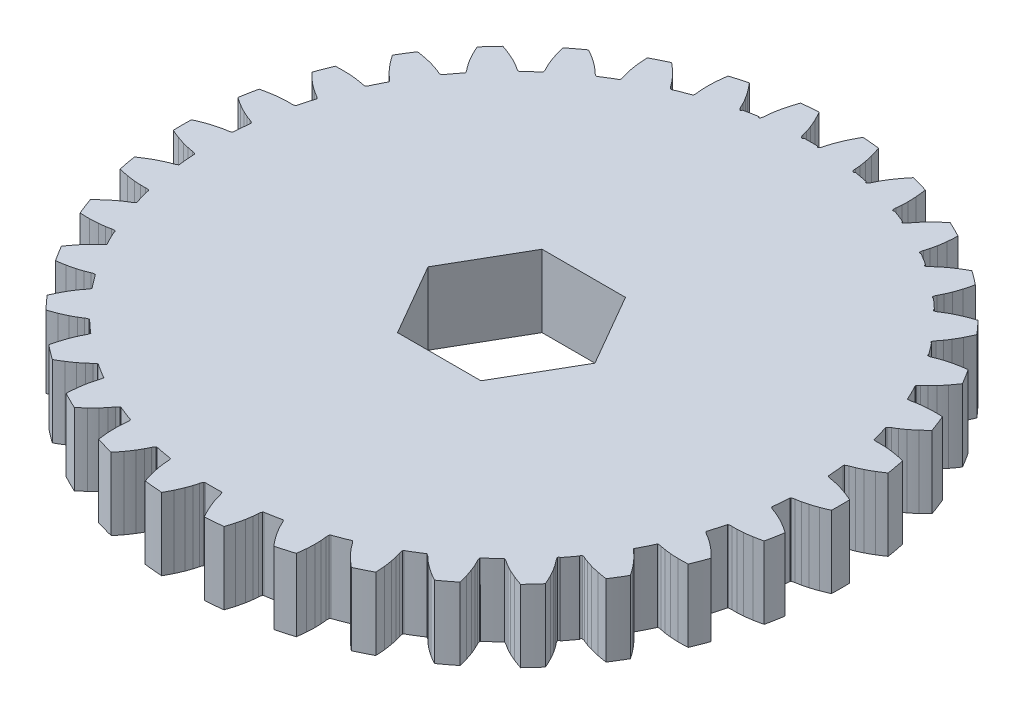
SolidWorks part; units mm, degrees
ref_plane "Front Plane" through (0, 0, 0) normal (0, 0, 1) x (1, 0, 0)
ref_plane "Top Plane" through (0, 0, 0) normal (0, 1, 0) x (1, 0, 0)
ref_plane "Right Plane" through (0, 0, 0) normal (1, 0, 0) x (0, 0, -1)
sketch "Model" plane through (0, 0, 0) normal (0, 1, 0) x (1, 0, 0)
  line L1 (7.3323, 0) -> (3.6662, 6.35)
  line L2 (3.6662, 6.35) -> (-3.6662, 6.35)
  line L3 (-3.6662, 6.35) -> (-7.3323, 0)
  line L4 (-7.3323, 0) -> (-3.6662, -6.35)
  line L5 (-3.6662, -6.35) -> (3.6662, -6.35)
  line L6 (3.6662, -6.35) -> (7.3323, 0)
  circle A0 centre (0, 0) radius 27.7 construction
  arc A1 (26.1185, -2.4202) -> (26.1766, -1.6798) centre (0, 0) ccw
  arc A2 (26.2183, -1.6388) -> (26.1766, -1.6798) centre (26.263, -1.726) ccw
  arc A3 (26.4889, -1.5535) -> (26.2183, -1.6388) centre (26.6041, -2.3907) ccw
  arc A4 (26.4889, -1.5535) -> (26.9416, -1.473) centre (25.6873, 4.2688) ccw
  arc A5 (26.9416, -1.473) -> (27.4742, -1.3382) centre (25.1508, 6.7249) ccw
  arc A6 (27.4742, -1.3382) -> (28.1662, -1.11) centre (24.8202, 7.8723) ccw
  arc A7 (28.1662, -1.11) -> (28.9229, -0.7986) centre (23.9466, 10.2174) ccw
  arc A8 (28.9229, -0.7986) -> (28.9229, 0.7986) centre (0, 0) ccw
  arc A9 (28.9229, 0.7986) -> (28.1662, 1.11) centre (23.9466, -10.2174) ccw
  arc A10 (28.1662, 1.11) -> (27.4742, 1.3382) centre (24.8202, -7.8723) ccw
  arc A11 (27.4742, 1.3382) -> (26.9416, 1.473) centre (25.1508, -6.7249) ccw
  arc A12 (26.9416, 1.473) -> (26.4889, 1.5535) centre (25.6873, -4.2688) ccw
  arc A13 (26.2183, 1.6388) -> (26.4889, 1.5535) centre (26.6041, 2.3907) ccw
  arc A14 (26.1675, 1.6852) -> (26.2183, 1.6388) centre (26.2566, 1.7318) ccw
  arc A15 (26.1675, 1.6852) -> (26.0357, 3.1176) centre (0, 0) ccw
  arc A16 (26.073, 3.2067) -> (26.0357, 3.1176) centre (26.133, 3.1292) ccw
  arc A17 (26.3233, 3.3403) -> (26.073, 3.2067) centre (26.5904, 2.5385) ccw
  arc A18 (26.3233, 3.3403) -> (26.7535, 3.5026) centre (24.4655, 8.9161) ccw
  arc A19 (26.7535, 3.5026) -> (27.2523, 3.7329) centre (23.4869, 11.2318) ccw
  arc A20 (27.2523, 3.7329) -> (27.8906, 4.0844) centre (22.951, 12.2989) ccw
  arc A21 (27.8906, 4.0844) -> (28.5771, 4.5296) centre (21.6614, 14.4436) ccw
  arc A22 (28.5771, 4.5296) -> (28.2837, 6.0995) centre (0, 0) ccw
  arc A23 (28.2837, 6.0995) -> (27.4827, 6.2666) centre (25.4163, -5.6432) ccw
  arc A24 (27.4827, 6.2666) -> (26.7605, 6.3638) centre (25.8441, -3.1775) ccw
  arc A25 (26.7605, 6.3638) -> (26.2122, 6.3984) centre (25.9582, -1.9889) ccw
  arc A26 (26.2122, 6.3984) -> (25.7524, 6.3943) centre (26.0343, 0.5239) ccw
  arc A27 (25.4707, 6.4285) -> (25.7524, 6.3943) centre (25.7119, 7.2385) ccw
  arc A28 (25.4168, 6.447) -> (25.4707, 6.4285) centre (25.4771, 6.5347) ccw
  arc A29 (25.4168, 6.447) -> (25.0195, 7.8485) centre (0, 0) ccw
  arc A30 (25.0398, 7.943) -> (25.0195, 7.8485) centre (25.113, 7.8779) ccw
  arc A31 (25.2613, 8.1203) -> (25.0398, 7.943) centre (25.6712, 7.3813) ccw
  arc A32 (25.2613, 8.1203) -> (25.6544, 8.3589) centre (22.4106, 13.2599) ccw
  arc A33 (25.6544, 8.3589) -> (26.1024, 8.677) centre (21.0231, 15.3563) ccw
  arc A34 (26.1024, 8.677) -> (26.6652, 9.1398) centre (20.3003, 16.3068) ccw
  arc A35 (26.6652, 9.1398) -> (27.2583, 9.7035) centre (18.6386, 18.1779) ccw
  arc A36 (27.2583, 9.7035) -> (26.6813, 11.1928) centre (0, 0) ccw
  arc A37 (26.6813, 11.1928) -> (25.8632, 11.2099) centre (26.0205, -0.8769) ccw
  arc A38 (25.8632, 11.2099) -> (25.1355, 11.1727) centre (25.9879, 1.6254) ccw
  arc A39 (25.1355, 11.1727) -> (24.5902, 11.1059) centre (25.8817, 2.8148) ccw
  arc A40 (24.5902, 11.1059) -> (24.139, 11.0175) centre (25.4948, 5.2988) ccw
  arc A41 (23.8558, 10.9993) -> (24.139, 11.0175) centre (23.944, 11.8398) ccw
  arc A42 (23.8034, 10.9988) -> (23.8558, 10.9993) centre (23.8287, 11.1089) ccw
  arc A43 (23.8034, 10.9988) -> (23.1514, 12.3122) centre (0, 0) ccw
  arc A44 (23.154, 12.4088) -> (23.1514, 12.3122) centre (23.2379, 12.3582) ccw
  arc A45 (23.3391, 12.6238) -> (23.154, 12.4088) centre (23.8778, 11.9727) ccw
  arc A46 (23.3391, 12.6238) -> (23.6816, 12.9306) centre (19.5926, 17.152) ccw
  arc A47 (23.6816, 12.9306) -> (24.0635, 13.3255) centre (17.8434, 18.9578) ccw
  arc A48 (24.0635, 13.3255) -> (24.5317, 13.8838) centre (16.9583, 19.7593) ccw
  arc A49 (24.5317, 13.8838) -> (25.0418, 14.5927) centre (14.981, 21.2932) ccw
  arc A50 (25.0418, 14.5927) -> (24.225, 15.9119) centre (0, 0) ccw
  arc A51 (24.225, 15.9119) -> (23.363, 15.7713) centre (25.7385, 3.9192) ccw
  arc A52 (23.363, 15.7713) -> (22.6546, 15.6011) centre (25.2467, 6.373) ccw
  arc A53 (22.6546, 15.6011) -> (22.1308, 15.4353) centre (24.9238, 7.5226) ccw
  arc A54 (22.1308, 15.4353) -> (21.7035, 15.2654) centre (24.087, 9.8932) ccw
  arc A55 (21.4285, 15.1955) -> (21.7035, 15.2654) centre (21.3607, 16.0379) ccw
  arc A56 (21.4336, 15.196) -> (21.4285, 15.1955) centre (21.4207, 15.2932) ccw
  arc A57 (21.4336, 15.196) -> (20.5895, 16.3215) centre (0, 0) ccw
  arc A58 (20.4796, 16.4521) -> (20.5895, 16.3215) centre (20.5714, 16.4178) ccw
  arc A59 (20.6221, 16.6974) -> (20.4796, 16.4521) centre (21.2713, 16.1563) ccw
  arc A60 (20.6221, 16.6974) -> (20.9024, 17.0619) centre (16.1073, 20.4601) ccw
  arc A61 (20.9024, 17.0619) -> (21.2052, 17.5203) centre (14.0561, 21.9137) ccw
  arc A62 (21.2052, 17.5203) -> (21.5629, 18.1551) centre (13.0388, 22.5389) ccw
  arc A63 (21.5629, 18.1551) -> (21.9401, 18.96) centre (10.8133, 23.6834) ccw
  arc A64 (21.9401, 18.96) -> (20.9035, 20.0971) centre (0, 0) ccw
  arc A65 (20.9035, 20.0971) -> (20.0673, 19.7958) centre (24.5801, 8.582) ccw
  arc A66 (20.0673, 19.7958) -> (19.4021, 19.4982) centre (23.6458, 10.9036) ccw
  arc A67 (19.4021, 19.4982) -> (18.9177, 19.239) centre (23.1172, 11.9742) ccw
  arc A68 (18.9177, 19.239) -> (18.5289, 18.9935) centre (21.859, 14.1507) ccw
  arc A69 (18.2715, 18.8742) -> (18.5289, 18.9935) centre (18.0501, 19.6899) ccw
  arc A70 (18.2887, 18.8807) -> (18.2715, 18.8742) centre (18.2458, 18.9688) ccw
  arc A71 (18.2887, 18.8807) -> (17.2519, 19.8325) centre (0, 0) ccw
  arc A72 (17.1078, 19.935) -> (17.2519, 19.8325) centre (17.2044, 19.9182) ccw
  arc A73 (17.2028, 20.2024) -> (17.1078, 19.935) centre (17.9404, 19.7898) ccw
  arc A74 (17.2028, 20.2024) -> (17.4114, 20.6122) centre (12.0735, 23.0714) ccw
  arc A75 (17.4114, 20.6122) -> (17.6248, 21.1184) centre (9.7902, 24.1234) ccw
  arc A76 (17.6248, 21.1184) -> (17.8597, 21.8082) centre (8.6753, 24.551) ccw
  arc A77 (17.8597, 21.8082) -> (18.0855, 22.6818) centre (6.2774, 25.2671) ccw
  arc A78 (18.0855, 22.6818) -> (16.8666, 23.6023) centre (0, 0) ccw
  arc A79 (16.8666, 23.6023) -> (16.0881, 23.146) centre (22.5847, 12.9524) ccw
  arc A80 (16.0881, 23.146) -> (15.489, 22.7314) centre (21.2397, 15.0628) ccw
  arc A81 (15.489, 22.7314) -> (15.0605, 22.3875) centre (20.5233, 16.0181) ccw
  arc A82 (15.0605, 22.3875) -> (14.7234, 22.0748) centre (18.8866, 17.9264) ccw
  arc A83 (14.4923, 21.9102) -> (14.7234, 22.0748) centre (14.1247, 22.6713) ccw
  arc A84 (14.5162, 21.9266) -> (14.4923, 21.9102) centre (14.4496, 21.9985) ccw
  arc A85 (14.5162, 21.9266) -> (13.3218, 22.6721) centre (0, 0) ccw
  arc A86 (13.1535, 22.7392) -> (13.3218, 22.6721) centre (13.2515, 22.7404) ccw
  arc A87 (13.1977, 23.0194) -> (13.1535, 22.7392) centre (13.9986, 22.7494) ccw
  arc A88 (13.1977, 23.0194) -> (13.3275, 23.4605) centre (7.6285, 24.8971) ccw
  arc A89 (13.3275, 23.4605) -> (13.4442, 23.9974) centre (5.1908, 25.5116) ccw
  arc A90 (13.4442, 23.9974) -> (13.5484, 24.7186) centre (4.0163, 25.7271) ccw
  arc A91 (13.5484, 24.7186) -> (13.6101, 25.6297) centre (1.5277, 25.9904) ccw
  arc A92 (13.6101, 25.6297) -> (12.251, 26.3064) centre (0, 0) ccw
  arc A93 (12.251, 26.3064) -> (11.5611, 25.7081) centre (19.8201, 16.8818) ccw
  arc A94 (11.5611, 25.7081) -> (11.0484, 25.1904) centre (18.1103, 18.7091) ccw
  arc A95 (11.0484, 25.1904) -> (10.6903, 24.7737) centre (17.2305, 19.5165) ccw
  arc A96 (10.6903, 24.7737) -> (10.4165, 24.4043) centre (15.2711, 21.0916) ccw
  arc A97 (10.2195, 24.2001) -> (10.4165, 24.4043) centre (9.7184, 24.8807) ccw
  arc A98 (10.2447, 24.2274) -> (10.2195, 24.2001) centre (10.1614, 24.279) ccw
  arc A99 (10.2447, 24.2274) -> (8.9332, 24.741) centre (0, 0) ccw
  arc A100 (8.7512, 24.7689) -> (8.9332, 24.741) centre (8.8473, 24.7881) ccw
  arc A101 (8.7432, 25.0526) -> (8.7512, 24.7689) centre (9.58, 24.9343) ccw
  arc A102 (8.7432, 25.0526) -> (8.7897, 25.51) centre (2.9238, 25.8749) ccw
  arc A103 (8.7897, 25.51) -> (8.8058, 26.0592) centre (0.4147, 26.031) ccw
  arc A104 (8.8058, 26.0592) -> (8.7757, 26.7872) centre (-0.7794, 26.027) ccw
  arc A105 (8.7757, 26.7872) -> (8.6677, 27.702) centre (-3.2741, 25.8285) ccw
  arc A106 (8.6677, 27.702) -> (7.2138, 28.1157) centre (0, 0) ccw
  arc A107 (7.2138, 28.1157) -> (6.6404, 27.3947) centre (16.3806, 20.2363) ccw
  arc A108 (6.6404, 27.3947) -> (6.2315, 26.7916) centre (14.3641, 21.7183) ccw
  arc A109 (6.2315, 26.7916) -> (5.9562, 26.3162) centre (13.351, 22.3503) ccw
  arc A110 (5.9562, 26.3162) -> (5.7549, 25.9028) centre (11.1355, 23.5385) ccw
  arc A111 (5.5987, 25.6659) -> (5.7549, 25.9028) centre (4.9811, 26.2428) ccw
  arc A112 (5.6203, 25.7026) -> (5.5987, 25.6659) centre (5.5271, 25.7328) ccw
  arc A113 (5.6203, 25.7026) -> (4.2365, 25.9665) centre (0, 0) ccw
  arc A114 (4.0509, 25.9552) -> (4.2365, 25.9665) centre (4.1419, 25.9917) ccw
  arc A115 (3.9909, 26.2325) -> (4.0509, 25.9552) centre (4.8352, 26.2701) ccw
  arc A116 (3.9909, 26.2325) -> (3.9526, 26.6907) centre (-1.8805, 25.9716) ccw
  arc A117 (3.9526, 26.6907) -> (3.8675, 27.2335) centre (-4.3756, 25.664) ccw
  arc A118 (3.8675, 27.2335) -> (3.7041, 27.9436) centre (-5.5486, 25.4406) ccw
  arc A119 (3.7041, 27.9436) -> (3.4283, 28.8275) centre (-7.9643, 24.7872) ccw
  arc A120 (3.4283, 28.8275) -> (1.9271, 28.9666) centre (0, 0) ccw
  arc A121 (1.9271, 28.9666) -> (1.4936, 28.1485) centre (12.3833, 22.9017) ccw
  arc A122 (1.4936, 28.1485) -> (1.2025, 27.4805) centre (10.1288, 23.9879) ccw
  arc A123 (1.2025, 27.4805) -> (1.0191, 26.9626) centre (9.0168, 24.423) ccw
  arc A124 (1.0191, 26.9626) -> (0.8972, 26.5192) centre (6.6207, 25.1839) ccw
  arc A125 (0.7873, 26.2576) -> (0.8972, 26.5192) centre (0.0742, 26.7112) ccw
  arc A126 (0.8021, 26.3003) -> (0.7873, 26.2576) centre (0.7046, 26.3102) ccw
  arc A127 (0.8021, 26.3003) -> (-0.6068, 26.3056) centre (0, 0) ccw
  arc A128 (-0.7873, 26.2576) -> (-0.6068, 26.3056) centre (-0.7046, 26.3102) ccw
  arc A129 (-0.8972, 26.5192) -> (-0.7873, 26.2576) centre (-0.0742, 26.7112) ccw
  arc A130 (-0.8972, 26.5192) -> (-1.0191, 26.9626) centre (-6.6207, 25.1839) ccw
  arc A131 (-1.0191, 26.9626) -> (-1.2025, 27.4805) centre (-9.0168, 24.423) ccw
  arc A132 (-1.2025, 27.4805) -> (-1.4936, 28.1485) centre (-10.1288, 23.9879) ccw
  arc A133 (-1.4936, 28.1485) -> (-1.9277, 28.9676) centre (-12.3833, 22.9017) ccw
  arc A134 (-1.9277, 28.9676) -> (-3.4279, 28.8286) centre (0, 0) ccw
  arc A135 (-3.4279, 28.8286) -> (-3.7041, 27.9436) centre (7.9643, 24.7872) ccw
  arc A136 (-3.7041, 27.9436) -> (-3.8675, 27.2335) centre (5.5486, 25.4406) ccw
  arc A137 (-3.8675, 27.2335) -> (-3.9526, 26.6907) centre (4.3756, 25.664) ccw
  arc A138 (-3.9526, 26.6907) -> (-3.9909, 26.2325) centre (1.8805, 25.9716) ccw
  arc A139 (-4.0509, 25.9552) -> (-3.9909, 26.2325) centre (-4.8352, 26.2701) ccw
  arc A140 (-4.0442, 25.9995) -> (-4.0509, 25.9552) centre (-4.1419, 25.9917) ccw
  arc A141 (-4.0442, 25.9995) -> (-5.43, 25.7458) centre (0, 0) ccw
  arc A142 (-5.5987, 25.6659) -> (-5.43, 25.7458) centre (-5.5271, 25.7328) ccw
  arc A143 (-5.7549, 25.9028) -> (-5.5987, 25.6659) centre (-4.9811, 26.2428) ccw
  arc A144 (-5.7549, 25.9028) -> (-5.9562, 26.3162) centre (-11.1355, 23.5385) ccw
  arc A145 (-5.9562, 26.3162) -> (-6.2315, 26.7916) centre (-13.351, 22.3503) ccw
  arc A146 (-6.2315, 26.7916) -> (-6.6404, 27.3947) centre (-14.3641, 21.7183) ccw
  arc A147 (-6.6404, 27.3947) -> (-7.2161, 28.1184) centre (-16.3806, 20.2363) ccw
  arc A148 (-7.2161, 28.1184) -> (-8.6671, 27.7055) centre (0, 0) ccw
  arc A149 (-8.6671, 27.7055) -> (-8.7757, 26.7872) centre (3.2741, 25.8285) ccw
  arc A150 (-8.7757, 26.7872) -> (-8.8058, 26.0592) centre (0.7794, 26.027) ccw
  arc A151 (-8.8058, 26.0592) -> (-8.7897, 25.51) centre (-0.4147, 26.031) ccw
  arc A152 (-8.7897, 25.51) -> (-8.7432, 25.0526) centre (-2.9238, 25.8749) ccw
  arc A153 (-8.7512, 24.7689) -> (-8.7432, 25.0526) centre (-9.58, 24.9343) ccw
  arc A154 (-8.7401, 24.7222) -> (-8.7512, 24.7689) centre (-8.8779, 24.7141) ccw
  arc A155 (-8.7401, 24.7222) -> (-10.1236, 24.1886) centre (0, 0) ccw
  arc A156 (-10.2195, 24.2001) -> (-10.1236, 24.1886) centre (-10.1614, 24.279) ccw
  arc A157 (-10.4165, 24.4043) -> (-10.2195, 24.2001) centre (-9.7184, 24.8807) ccw
  arc A158 (-10.4165, 24.4043) -> (-10.6903, 24.7737) centre (-15.2711, 21.0916) ccw
  arc A159 (-10.6903, 24.7737) -> (-11.0484, 25.1904) centre (-17.2305, 19.5165) ccw
  arc A160 (-11.0484, 25.1904) -> (-11.5611, 25.7081) centre (-18.1103, 18.7091) ccw
  arc A161 (-11.5611, 25.7081) -> (-12.1772, 26.2467) centre (-19.8201, 16.8818) ccw
  arc A162 (-12.1772, 26.2467) -> (-13.6069, 25.5347) centre (0, 0) ccw
  arc A163 (-13.6069, 25.5347) -> (-13.5484, 24.7186) centre (-1.5277, 25.9904) ccw
  arc A164 (-13.5484, 24.7186) -> (-13.4442, 23.9974) centre (-4.0163, 25.7271) ccw
  arc A165 (-13.4442, 23.9974) -> (-13.3275, 23.4605) centre (-5.1908, 25.5116) ccw
  arc A166 (-13.3275, 23.4605) -> (-13.1977, 23.0194) centre (-7.6285, 24.8971) ccw
  arc A167 (-13.1535, 22.7392) -> (-13.1977, 23.0194) centre (-13.9986, 22.7494) ccw
  arc A168 (-13.1353, 22.6945) -> (-13.1535, 22.7392) centre (-13.2668, 22.6671) ccw
  arc A169 (-13.1353, 22.6945) -> (-14.3959, 21.9166) centre (0, 0) ccw
  arc A170 (-14.4923, 21.9102) -> (-14.3959, 21.9166) centre (-14.4496, 21.9985) ccw
  arc A171 (-14.7234, 22.0748) -> (-14.4923, 21.9102) centre (-14.1247, 22.6713) ccw
  arc A172 (-14.7234, 22.0748) -> (-15.0605, 22.3875) centre (-18.8866, 17.9264) ccw
  arc A173 (-15.0605, 22.3875) -> (-15.489, 22.7314) centre (-20.5233, 16.0181) ccw
  arc A174 (-15.489, 22.7314) -> (-16.0881, 23.146) centre (-21.2397, 15.0628) ccw
  arc A175 (-16.0881, 23.146) -> (-16.7926, 23.5622) centre (-22.5847, 12.9524) ccw
  arc A176 (-16.7926, 23.5622) -> (-18.0672, 22.5997) centre (0, 0) ccw
  arc A177 (-18.0672, 22.5997) -> (-17.8597, 21.8082) centre (-6.2774, 25.2671) ccw
  arc A178 (-17.8597, 21.8082) -> (-17.6248, 21.1184) centre (-8.6753, 24.551) ccw
  arc A179 (-17.6248, 21.1184) -> (-17.4114, 20.6122) centre (-9.7902, 24.1234) ccw
  arc A180 (-17.4114, 20.6122) -> (-17.2028, 20.2024) centre (-12.0735, 23.0714) ccw
  arc A181 (-17.1078, 19.935) -> (-17.2028, 20.2024) centre (-17.9404, 19.7898) ccw
  arc A182 (-17.0837, 19.8928) -> (-17.1078, 19.935) centre (-17.2059, 19.851) ccw
  arc A183 (-17.0837, 19.8928) -> (-18.1779, 18.8982) centre (0, 0) ccw
  arc A184 (-18.2715, 18.8742) -> (-18.1779, 18.8982) centre (-18.2458, 18.9688) ccw
  arc A185 (-18.5289, 18.9935) -> (-18.2715, 18.8742) centre (-18.0501, 19.6899) ccw
  arc A186 (-18.5289, 18.9935) -> (-18.9177, 19.239) centre (-21.859, 14.1507) ccw
  arc A187 (-18.9177, 19.239) -> (-19.4021, 19.4982) centre (-23.1172, 11.9742) ccw
  arc A188 (-19.4021, 19.4982) -> (-20.0673, 19.7958) centre (-23.6458, 10.9036) ccw
  arc A189 (-20.0673, 19.7958) -> (-20.8363, 20.0754) centre (-24.5801, 8.582) ccw
  arc A190 (-20.8363, 20.0754) -> (-21.9123, 18.8951) centre (0, 0) ccw
  arc A191 (-21.9123, 18.8951) -> (-21.5629, 18.1551) centre (-10.8133, 23.6834) ccw
  arc A192 (-21.5629, 18.1551) -> (-21.2052, 17.5203) centre (-13.0388, 22.5389) ccw
  arc A193 (-21.2052, 17.5203) -> (-20.9024, 17.0619) centre (-14.0561, 21.9137) ccw
  arc A194 (-20.9024, 17.0619) -> (-20.6221, 16.6974) centre (-16.1073, 20.4601) ccw
  arc A195 (-20.4796, 16.4521) -> (-20.6221, 16.6974) centre (-21.2713, 16.1563) ccw
  arc A196 (-20.4506, 16.4119) -> (-20.4796, 16.4521) centre (-20.5624, 16.3616) ccw
  arc A197 (-20.4506, 16.4119) -> (-21.3409, 15.2362) centre (0, 0) ccw
  arc A198 (-21.4285, 15.1955) -> (-21.3409, 15.2362) centre (-21.4207, 15.2932) ccw
  arc A199 (-21.7035, 15.2654) -> (-21.4285, 15.1955) centre (-21.3607, 16.0379) ccw
  arc A200 (-21.7035, 15.2654) -> (-22.1308, 15.4353) centre (-24.087, 9.8932) ccw
  arc A201 (-22.1308, 15.4353) -> (-22.6546, 15.6011) centre (-24.9238, 7.5226) ccw
  arc A202 (-22.6546, 15.6011) -> (-23.363, 15.7713) centre (-25.2467, 6.373) ccw
  arc A203 (-23.363, 15.7713) -> (-24.1703, 15.9049) centre (-25.7385, 3.9192) ccw
  arc A204 (-24.1703, 15.9049) -> (-25.0111, 14.547) centre (0, 0) ccw
  arc A205 (-25.0111, 14.547) -> (-24.5317, 13.8838) centre (-14.981, 21.2932) ccw
  arc A206 (-24.5317, 13.8838) -> (-24.0635, 13.3255) centre (-16.9583, 19.7593) ccw
  arc A207 (-24.0635, 13.3255) -> (-23.6816, 12.9306) centre (-17.8434, 18.9578) ccw
  arc A208 (-23.6816, 12.9306) -> (-23.3391, 12.6238) centre (-19.5926, 17.152) ccw
  arc A209 (-23.154, 12.4088) -> (-23.3391, 12.6238) centre (-23.8778, 11.9727) ccw
  arc A210 (-23.1209, 12.3694) -> (-23.154, 12.4088) centre (-23.2234, 12.3168) ccw
  arc A211 (-23.1209, 12.3694) -> (-23.7772, 11.0554) centre (0, 0) ccw
  arc A212 (-23.8558, 10.9993) -> (-23.7772, 11.0554) centre (-23.866, 11.0967) ccw
  arc A213 (-24.139, 11.0175) -> (-23.8558, 10.9993) centre (-23.944, 11.8398) ccw
  arc A214 (-24.139, 11.0175) -> (-24.5902, 11.1059) centre (-25.4948, 5.2988) ccw
  arc A215 (-24.5902, 11.1059) -> (-25.1355, 11.1727) centre (-25.8817, 2.8148) ccw
  arc A216 (-25.1355, 11.1727) -> (-25.8632, 11.2099) centre (-25.9879, 1.6254) ccw
  arc A217 (-25.8632, 11.2099) -> (-26.6813, 11.1928) centre (-26.0205, -0.8769) ccw
  arc A218 (-26.6813, 11.1928) -> (-27.2583, 9.7035) centre (0, 0) ccw
  arc A219 (-27.2583, 9.7035) -> (-26.6652, 9.1398) centre (-18.6386, 18.1779) ccw
  arc A220 (-26.6652, 9.1398) -> (-26.1024, 8.677) centre (-20.3003, 16.3068) ccw
  arc A221 (-26.1024, 8.677) -> (-25.6544, 8.3589) centre (-21.0231, 15.3563) ccw
  arc A222 (-25.6544, 8.3589) -> (-25.2613, 8.1203) centre (-22.4106, 13.2599) ccw
  arc A223 (-25.0398, 7.943) -> (-25.2613, 8.1203) centre (-25.6712, 7.3813) ccw
  arc A224 (-25.0029, 7.9012) -> (-25.0398, 7.943) centre (-25.0995, 7.8532) ccw
  arc A225 (-25.0029, 7.9012) -> (-25.4038, 6.4981) centre (0, 0) ccw
  arc A226 (-25.4707, 6.4285) -> (-25.4038, 6.4981) centre (-25.4987, 6.5224) ccw
  arc A227 (-25.7524, 6.3943) -> (-25.4707, 6.4285) centre (-25.7119, 7.2385) ccw
  arc A228 (-25.7524, 6.3943) -> (-26.2122, 6.3984) centre (-26.0343, 0.5239) ccw
  arc A229 (-26.2122, 6.3984) -> (-26.7605, 6.3638) centre (-25.9582, -1.9889) ccw
  arc A230 (-26.7605, 6.3638) -> (-27.4827, 6.2666) centre (-25.8441, -3.1775) ccw
  arc A231 (-27.4827, 6.2666) -> (-28.2837, 6.0995) centre (-25.4163, -5.6432) ccw
  arc A232 (-28.2837, 6.0995) -> (-28.5771, 4.5296) centre (0, 0) ccw
  arc A233 (-28.5771, 4.5296) -> (-27.8906, 4.0844) centre (-21.6614, 14.4436) ccw
  arc A234 (-27.8906, 4.0844) -> (-27.2523, 3.7329) centre (-22.951, 12.2989) ccw
  arc A235 (-27.2523, 3.7329) -> (-26.7535, 3.5026) centre (-23.4869, 11.2318) ccw
  arc A236 (-26.7535, 3.5026) -> (-26.3233, 3.3403) centre (-24.4655, 8.9161) ccw
  arc A237 (-26.073, 3.2067) -> (-26.3233, 3.3403) centre (-26.5904, 2.5385) ccw
  arc A238 (-26.0313, 3.1538) -> (-26.073, 3.2067) centre (-26.1269, 3.1214) ccw
  arc A239 (-26.0313, 3.1538) -> (-26.1652, 1.7195) centre (0, 0) ccw
  arc A240 (-26.2183, 1.6388) -> (-26.1652, 1.7195) centre (-26.263, 1.726) ccw
  arc A241 (-26.4889, 1.5535) -> (-26.2183, 1.6388) centre (-26.6041, 2.3907) ccw
  arc A242 (-26.4889, 1.5535) -> (-26.9416, 1.473) centre (-25.6873, -4.2688) ccw
  arc A243 (-26.9416, 1.473) -> (-27.4742, 1.3382) centre (-25.1508, -6.7249) ccw
  arc A244 (-27.4742, 1.3382) -> (-28.1662, 1.11) centre (-24.8202, -7.8723) ccw
  arc A245 (-28.1662, 1.11) -> (-28.9229, 0.7986) centre (-23.9466, -10.2174) ccw
  arc A246 (-28.9229, 0.7986) -> (-28.9229, -0.7986) centre (0, 0) ccw
  arc A247 (-28.9229, -0.7986) -> (-28.1662, -1.11) centre (-23.9466, 10.2174) ccw
  arc A248 (-28.1662, -1.11) -> (-27.4742, -1.3382) centre (-24.8202, 7.8723) ccw
  arc A249 (-27.4742, -1.3382) -> (-26.9416, -1.473) centre (-25.1508, 6.7249) ccw
  arc A250 (-26.9416, -1.473) -> (-26.4889, -1.5535) centre (-25.6873, 4.2688) ccw
  arc A251 (-26.2183, -1.6388) -> (-26.4889, -1.5535) centre (-26.6041, -2.3907) ccw
  arc A252 (-26.1719, -1.762) -> (-26.2183, -1.6388) centre (-26.263, -1.726) ccw
  arc A253 (-26.1719, -1.762) -> (-26.0401, -3.1604) centre (0, 0) ccw
  arc A254 (-26.073, -3.2067) -> (-26.0401, -3.1604) centre (-26.133, -3.1292) ccw
  arc A255 (-26.3233, -3.3403) -> (-26.073, -3.2067) centre (-26.5904, -2.5385) ccw
  arc A256 (-26.3233, -3.3403) -> (-26.7535, -3.5026) centre (-24.4655, -8.9161) ccw
  arc A257 (-26.7535, -3.5026) -> (-27.2523, -3.7329) centre (-23.4869, -11.2318) ccw
  arc A258 (-27.2523, -3.7329) -> (-27.8906, -4.0844) centre (-22.951, -12.2989) ccw
  arc A259 (-27.8906, -4.0844) -> (-28.595, -4.5421) centre (-21.6614, -14.4436) ccw
  arc A260 (-28.595, -4.5421) -> (-28.3049, -6.0944) centre (0, 0) ccw
  arc A261 (-28.3049, -6.0944) -> (-27.4827, -6.2666) centre (-25.4163, 5.6432) ccw
  arc A262 (-27.4827, -6.2666) -> (-26.7605, -6.3638) centre (-25.8441, 3.1775) ccw
  arc A263 (-26.7605, -6.3638) -> (-26.2122, -6.3984) centre (-25.9582, 1.9889) ccw
  arc A264 (-26.2122, -6.3984) -> (-25.7524, -6.3943) centre (-26.0343, -0.5239) ccw
  arc A265 (-25.4707, -6.4285) -> (-25.7524, -6.3943) centre (-25.7119, -7.2385) ccw
  arc A266 (-25.4134, -6.5706) -> (-25.4707, -6.4285) centre (-25.4987, -6.5224) ccw
  arc A267 (-25.4134, -6.5706) -> (-25.0253, -7.9214) centre (0, 0) ccw
  arc A268 (-25.0398, -7.943) -> (-25.0253, -7.9214) centre (-25.113, -7.8779) ccw
  arc A269 (-25.2613, -8.1203) -> (-25.0398, -7.943) centre (-25.6712, -7.3813) ccw
  arc A270 (-25.2613, -8.1203) -> (-25.6544, -8.3589) centre (-22.4106, -13.2599) ccw
  arc A271 (-25.6544, -8.3589) -> (-26.1024, -8.677) centre (-21.0231, -15.3563) ccw
  arc A272 (-26.1024, -8.677) -> (-26.6652, -9.1398) centre (-20.3003, -16.3068) ccw
  arc A273 (-26.6652, -9.1398) -> (-27.288, -9.7339) centre (-18.6386, -18.1779) ccw
  arc A274 (-27.288, -9.7339) -> (-26.7237, -11.1904) centre (0, 0) ccw
  arc A275 (-26.7237, -11.1904) -> (-25.8632, -11.2099) centre (-26.0205, 0.8769) ccw
  arc A276 (-25.8632, -11.2099) -> (-25.1355, -11.1727) centre (-25.9879, -1.6254) ccw
  arc A277 (-25.1355, -11.1727) -> (-24.5902, -11.1059) centre (-25.8817, -2.8148) ccw
  arc A278 (-24.5902, -11.1059) -> (-24.139, -11.0175) centre (-25.4948, -5.2988) ccw
  arc A279 (-23.8558, -10.9993) -> (-24.139, -11.0175) centre (-23.944, -11.8398) ccw
  arc A280 (-23.7824, -11.1478) -> (-23.8558, -10.9993) centre (-23.866, -11.0967) ccw
  arc A281 (-23.7824, -11.1478) -> (-23.1517, -12.4048) centre (0, 0) ccw
  arc A282 (-23.154, -12.4088) -> (-23.1517, -12.4048) centre (-23.2379, -12.3582) ccw
  arc A283 (-23.3391, -12.6238) -> (-23.154, -12.4088) centre (-23.8778, -11.9727) ccw
  arc A284 (-23.3391, -12.6238) -> (-23.6816, -12.9306) centre (-19.5926, -17.152) ccw
  arc A285 (-23.6816, -12.9306) -> (-24.0635, -13.3255) centre (-17.8434, -18.9578) ccw
  arc A286 (-24.0635, -13.3255) -> (-24.5317, -13.8838) centre (-16.9583, -19.7593) ccw
  arc A287 (-24.5317, -13.8838) -> (-25.0111, -14.547) centre (-14.981, -21.2932) ccw
  arc A288 (-25.0111, -14.547) -> (-24.1703, -15.9049) centre (0, 0) ccw
  arc A289 (-24.1703, -15.9049) -> (-23.363, -15.7713) centre (-25.7385, -3.9192) ccw
  arc A290 (-23.363, -15.7713) -> (-22.6546, -15.6011) centre (-25.2467, -6.373) ccw
  arc A291 (-22.6546, -15.6011) -> (-22.1308, -15.4353) centre (-24.9238, -7.5226) ccw
  arc A292 (-22.1308, -15.4353) -> (-21.7035, -15.2654) centre (-24.087, -9.8932) ccw
  arc A293 (-21.4285, -15.1955) -> (-21.7035, -15.2654) centre (-21.3607, -16.0379) ccw
  arc A294 (-21.3409, -15.2362) -> (-21.4285, -15.1955) centre (-21.4207, -15.2932) ccw
  arc A295 (-21.3409, -15.2362) -> (-20.4506, -16.4119) centre (0, 0) ccw
  arc A296 (-20.4796, -16.4521) -> (-20.4506, -16.4119) centre (-20.5624, -16.3616) ccw
  arc A297 (-20.6221, -16.6974) -> (-20.4796, -16.4521) centre (-21.2713, -16.1563) ccw
  arc A298 (-20.6221, -16.6974) -> (-20.9024, -17.0619) centre (-16.1073, -20.4601) ccw
  arc A299 (-20.9024, -17.0619) -> (-21.2052, -17.5203) centre (-14.0561, -21.9137) ccw
  arc A300 (-21.2052, -17.5203) -> (-21.5629, -18.1551) centre (-13.0388, -22.5389) ccw
  arc A301 (-21.5629, -18.1551) -> (-21.9123, -18.8951) centre (-10.8133, -23.6834) ccw
  arc A302 (-21.9123, -18.8951) -> (-20.8363, -20.0754) centre (0, 0) ccw
  arc A303 (-20.8363, -20.0754) -> (-20.0673, -19.7958) centre (-24.5801, -8.582) ccw
  arc A304 (-20.0673, -19.7958) -> (-19.4021, -19.4982) centre (-23.6458, -10.9036) ccw
  arc A305 (-19.4021, -19.4982) -> (-18.9177, -19.239) centre (-23.1172, -11.9742) ccw
  arc A306 (-18.9177, -19.239) -> (-18.5289, -18.9935) centre (-21.859, -14.1507) ccw
  arc A307 (-18.2715, -18.8742) -> (-18.5289, -18.9935) centre (-18.0501, -19.6899) ccw
  arc A308 (-18.1779, -18.8982) -> (-18.2715, -18.8742) centre (-18.2458, -18.9688) ccw
  arc A309 (-18.1779, -18.8982) -> (-17.0837, -19.8928) centre (0, 0) ccw
  arc A310 (-17.1078, -19.935) -> (-17.0837, -19.8928) centre (-17.2059, -19.851) ccw
  arc A311 (-17.2028, -20.2024) -> (-17.1078, -19.935) centre (-17.9404, -19.7898) ccw
  arc A312 (-17.2028, -20.2024) -> (-17.4114, -20.6122) centre (-12.0735, -23.0714) ccw
  arc A313 (-17.4114, -20.6122) -> (-17.6248, -21.1184) centre (-9.7902, -24.1234) ccw
  arc A314 (-17.6248, -21.1184) -> (-17.8597, -21.8082) centre (-8.6753, -24.551) ccw
  arc A315 (-17.8597, -21.8082) -> (-18.0672, -22.5997) centre (-6.2774, -25.2671) ccw
  arc A316 (-18.0672, -22.5997) -> (-16.7926, -23.5622) centre (0, 0) ccw
  arc A317 (-16.7926, -23.5622) -> (-16.0881, -23.146) centre (-22.5847, -12.9524) ccw
  arc A318 (-16.0881, -23.146) -> (-15.489, -22.7314) centre (-21.2397, -15.0628) ccw
  arc A319 (-15.489, -22.7314) -> (-15.0605, -22.3875) centre (-20.5233, -16.0181) ccw
  arc A320 (-15.0605, -22.3875) -> (-14.7234, -22.0748) centre (-18.8866, -17.9264) ccw
  arc A321 (-14.4923, -21.9102) -> (-14.7234, -22.0748) centre (-14.1247, -22.6713) ccw
  arc A322 (-14.3959, -21.9166) -> (-14.4923, -21.9102) centre (-14.4496, -21.9985) ccw
  arc A323 (-14.3959, -21.9166) -> (-13.1353, -22.6945) centre (0, 0) ccw
  arc A324 (-13.1535, -22.7392) -> (-13.1353, -22.6945) centre (-13.2668, -22.6671) ccw
  arc A325 (-13.1977, -23.0194) -> (-13.1535, -22.7392) centre (-13.9986, -22.7494) ccw
  arc A326 (-13.1977, -23.0194) -> (-13.3275, -23.4605) centre (-7.6285, -24.8971) ccw
  arc A327 (-13.3275, -23.4605) -> (-13.4442, -23.9974) centre (-5.1908, -25.5116) ccw
  arc A328 (-13.4442, -23.9974) -> (-13.5484, -24.7186) centre (-4.0163, -25.7271) ccw
  arc A329 (-13.5484, -24.7186) -> (-13.6069, -25.5347) centre (-1.5277, -25.9904) ccw
  arc A330 (-13.6069, -25.5347) -> (-12.1772, -26.2467) centre (0, 0) ccw
  arc A331 (-12.1772, -26.2467) -> (-11.5611, -25.7081) centre (-19.8201, -16.8818) ccw
  arc A332 (-11.5611, -25.7081) -> (-11.0484, -25.1904) centre (-18.1103, -18.7091) ccw
  arc A333 (-11.0484, -25.1904) -> (-10.6903, -24.7737) centre (-17.2305, -19.5165) ccw
  arc A334 (-10.6903, -24.7737) -> (-10.4165, -24.4043) centre (-15.2711, -21.0916) ccw
  arc A335 (-10.2195, -24.2001) -> (-10.4165, -24.4043) centre (-9.7184, -24.8807) ccw
  arc A336 (-10.1236, -24.1886) -> (-10.2195, -24.2001) centre (-10.1614, -24.279) ccw
  arc A337 (-10.1236, -24.1886) -> (-8.7401, -24.7222) centre (0, 0) ccw
  arc A338 (-8.7512, -24.7689) -> (-8.7401, -24.7222) centre (-8.8779, -24.7141) ccw
  arc A339 (-8.7432, -25.0526) -> (-8.7512, -24.7689) centre (-9.58, -24.9343) ccw
  arc A340 (-8.7432, -25.0526) -> (-8.7897, -25.51) centre (-2.9238, -25.8749) ccw
  arc A341 (-8.7897, -25.51) -> (-8.8058, -26.0592) centre (-0.4147, -26.031) ccw
  arc A342 (-8.8058, -26.0592) -> (-8.7757, -26.7872) centre (0.7794, -26.027) ccw
  arc A343 (-8.7757, -26.7872) -> (-8.6832, -27.6002) centre (3.2741, -25.8285) ccw
  arc A344 (-8.6832, -27.6002) -> (-7.147, -28.0373) centre (0, 0) ccw
  arc A345 (-7.147, -28.0373) -> (-6.6404, -27.3947) centre (-16.3806, -20.2363) ccw
  arc A346 (-6.6404, -27.3947) -> (-6.2315, -26.7916) centre (-14.3641, -21.7183) ccw
  arc A347 (-6.2315, -26.7916) -> (-5.9562, -26.3162) centre (-13.351, -22.3503) ccw
  arc A348 (-5.9562, -26.3162) -> (-5.7549, -25.9028) centre (-11.1355, -23.5385) ccw
  arc A349 (-5.5987, -25.6659) -> (-5.7549, -25.9028) centre (-4.9811, -26.2428) ccw
  arc A350 (-5.5066, -25.637) -> (-5.5987, -25.6659) centre (-5.5271, -25.7328) ccw
  arc A351 (-5.5066, -25.637) -> (-4.0478, -25.9074) centre (0, 0) ccw
  arc A352 (-4.0509, -25.9552) -> (-4.0478, -25.9074) centre (-4.187, -25.9223) ccw
  arc A353 (-3.9909, -26.2325) -> (-4.0509, -25.9552) centre (-4.8352, -26.2701) ccw
  arc A354 (-3.9909, -26.2325) -> (-3.9526, -26.6907) centre (1.8805, -25.9716) ccw
  arc A355 (-3.9526, -26.6907) -> (-3.8675, -27.2335) centre (4.3756, -25.664) ccw
  arc A356 (-3.8675, -27.2335) -> (-3.7041, -27.9436) centre (5.5486, -25.4406) ccw
  arc A357 (-3.7041, -27.9436) -> (-3.4638, -28.7258) centre (7.9643, -24.7872) ccw
  arc A358 (-3.4638, -28.7258) -> (-1.8735, -28.8732) centre (0, 0) ccw
  arc A359 (-1.8735, -28.8732) -> (-1.4936, -28.1485) centre (-12.3833, -22.9017) ccw
  arc A360 (-1.4936, -28.1485) -> (-1.2025, -27.4805) centre (-10.1288, -23.9879) ccw
  arc A361 (-1.2025, -27.4805) -> (-1.0191, -26.9626) centre (-9.0168, -24.423) ccw
  arc A362 (-1.0191, -26.9626) -> (-0.8972, -26.5192) centre (-6.6207, -25.1839) ccw
  arc A363 (-0.7873, -26.2576) -> (-0.8972, -26.5192) centre (-0.0742, -26.7112) ccw
  arc A364 (-0.702, -26.2123) -> (-0.7873, -26.2576) centre (-0.7046, -26.3102) ccw
  arc A365 (-0.702, -26.2123) -> (0.7817, -26.21) centre (0, 0) ccw
  arc A366 (0.7873, -26.2576) -> (0.7817, -26.21) centre (0.6473, -26.2501) ccw
  arc A367 (0.8972, -26.5192) -> (0.7873, -26.2576) centre (0.0742, -26.7112) ccw
  arc A368 (0.8972, -26.5192) -> (1.0191, -26.9626) centre (6.6207, -25.1839) ccw
  arc A369 (1.0191, -26.9626) -> (1.2025, -27.4805) centre (9.0168, -24.423) ccw
  arc A370 (1.2025, -27.4805) -> (1.4936, -28.1485) centre (10.1288, -23.9879) ccw
  arc A371 (1.4936, -28.1485) -> (1.8735, -28.8732) centre (12.3833, -22.9017) ccw
  arc A372 (1.8735, -28.8732) -> (3.4638, -28.7258) centre (0, 0) ccw
  arc A373 (3.4638, -28.7258) -> (3.7041, -27.9436) centre (-7.9643, -24.7872) ccw
  arc A374 (3.7041, -27.9436) -> (3.8675, -27.2335) centre (-5.5486, -25.4406) ccw
  arc A375 (3.8675, -27.2335) -> (3.9526, -26.6907) centre (-4.3756, -25.664) ccw
  arc A376 (3.9526, -26.6907) -> (3.9909, -26.2325) centre (-1.8805, -25.9716) ccw
  arc A377 (4.0509, -25.9552) -> (3.9909, -26.2325) centre (4.8352, -26.2701) ccw
  arc A378 (4.1264, -25.895) -> (4.0509, -25.9552) centre (4.1419, -25.9917) ccw
  arc A379 (4.1264, -25.895) -> (5.5839, -25.6203) centre (0, 0) ccw
  arc A380 (5.5987, -25.6659) -> (5.5839, -25.6203) centre (5.4613, -25.6853) ccw
  arc A381 (5.7549, -25.9028) -> (5.5987, -25.6659) centre (4.9811, -26.2428) ccw
  arc A382 (5.7549, -25.9028) -> (5.9562, -26.3162) centre (11.1355, -23.5385) ccw
  arc A383 (5.9562, -26.3162) -> (6.2315, -26.7916) centre (13.351, -22.3503) ccw
  arc A384 (6.2315, -26.7916) -> (6.6404, -27.3947) centre (14.3641, -21.7183) ccw
  arc A385 (6.6404, -27.3947) -> (7.147, -28.0373) centre (16.3806, -20.2363) ccw
  arc A386 (7.147, -28.0373) -> (8.6832, -27.6002) centre (0, 0) ccw
  arc A387 (8.6832, -27.6002) -> (8.7757, -26.7872) centre (-3.2741, -25.8285) ccw
  arc A388 (8.7757, -26.7872) -> (8.8058, -26.0592) centre (-0.7794, -26.027) ccw
  arc A389 (8.8058, -26.0592) -> (8.7897, -25.51) centre (0.4147, -26.031) ccw
  arc A390 (8.7897, -25.51) -> (8.7432, -25.0526) centre (2.9238, -25.8749) ccw
  arc A391 (8.7512, -24.7689) -> (8.7432, -25.0526) centre (9.58, -24.9343) ccw
  arc A392 (8.8144, -24.6958) -> (8.7512, -24.7689) centre (8.8473, -24.7881) ccw
  arc A393 (8.8144, -24.6958) -> (10.1954, -24.1585) centre (0, 0) ccw
  arc A394 (10.2195, -24.2001) -> (10.1954, -24.1585) centre (10.0918, -24.2462) ccw
  arc A395 (10.4165, -24.4043) -> (10.2195, -24.2001) centre (9.7184, -24.8807) ccw
  arc A396 (10.4165, -24.4043) -> (10.6903, -24.7737) centre (15.2711, -21.0916) ccw
  arc A397 (10.6903, -24.7737) -> (11.0484, -25.1904) centre (17.2305, -19.5165) ccw
  arc A398 (11.0484, -25.1904) -> (11.5611, -25.7081) centre (18.1103, -18.7091) ccw
  arc A399 (11.5611, -25.7081) -> (12.1772, -26.2467) centre (19.8201, -16.8818) ccw
  arc A400 (12.1772, -26.2467) -> (13.6069, -25.5347) centre (0, 0) ccw
  arc A401 (13.6069, -25.5347) -> (13.5484, -24.7186) centre (1.5277, -25.9904) ccw
  arc A402 (13.5484, -24.7186) -> (13.4442, -23.9974) centre (4.0163, -25.7271) ccw
  arc A403 (13.4442, -23.9974) -> (13.3275, -23.4605) centre (5.1908, -25.5116) ccw
  arc A404 (13.3275, -23.4605) -> (13.1977, -23.0194) centre (7.6285, -24.8971) ccw
  arc A405 (13.1535, -22.7392) -> (13.1977, -23.0194) centre (13.9986, -22.7494) ccw
  arc A406 (13.2021, -22.6557) -> (13.1535, -22.7392) centre (13.2515, -22.7404) ccw
  arc A407 (13.2021, -22.6557) -> (14.4592, -21.8748) centre (0, 0) ccw
  arc A408 (14.4923, -21.9102) -> (14.4592, -21.8748) centre (14.3814, -21.9806) ccw
  arc A409 (14.7234, -22.0748) -> (14.4923, -21.9102) centre (14.1247, -22.6713) ccw
  arc A410 (14.7234, -22.0748) -> (15.0605, -22.3875) centre (18.8866, -17.9264) ccw
  arc A411 (15.0605, -22.3875) -> (15.489, -22.7314) centre (20.5233, -16.0181) ccw
  arc A412 (15.489, -22.7314) -> (16.0881, -23.146) centre (21.2397, -15.0628) ccw
  arc A413 (16.0881, -23.146) -> (16.7926, -23.5622) centre (22.5847, -12.9524) ccw
  arc A414 (16.7926, -23.5622) -> (18.0672, -22.5997) centre (0, 0) ccw
  arc A415 (18.0672, -22.5997) -> (17.8597, -21.8082) centre (6.2774, -25.2671) ccw
  arc A416 (17.8597, -21.8082) -> (17.6248, -21.1184) centre (8.6753, -24.551) ccw
  arc A417 (17.6248, -21.1184) -> (17.4114, -20.6122) centre (9.7902, -24.1234) ccw
  arc A418 (17.4114, -20.6122) -> (17.2028, -20.2024) centre (12.0735, -23.0714) ccw
  arc A419 (17.1078, -19.935) -> (17.2028, -20.2024) centre (17.9404, -19.7898) ccw
  arc A420 (17.1403, -19.8441) -> (17.1078, -19.935) centre (17.2044, -19.9182) ccw
  arc A421 (17.1403, -19.8441) -> (18.2303, -18.8476) centre (0, 0) ccw
  arc A422 (18.2715, -18.8742) -> (18.2303, -18.8476) centre (18.1838, -18.9645) ccw
  arc A423 (18.5289, -18.9935) -> (18.2715, -18.8742) centre (18.0501, -19.6899) ccw
  arc A424 (18.5289, -18.9935) -> (18.9177, -19.239) centre (21.859, -14.1507) ccw
  arc A425 (18.9177, -19.239) -> (19.4021, -19.4982) centre (23.1172, -11.9742) ccw
  arc A426 (19.4021, -19.4982) -> (20.0673, -19.7958) centre (23.6458, -10.9036) ccw
  arc A427 (20.0673, -19.7958) -> (20.9035, -20.0971) centre (24.5801, -8.582) ccw
  arc A428 (20.9035, -20.0971) -> (21.9401, -18.96) centre (0, 0) ccw
  arc A429 (21.9401, -18.96) -> (21.5629, -18.1551) centre (10.8133, -23.6834) ccw
  arc A430 (21.5629, -18.1551) -> (21.2052, -17.5203) centre (13.0388, -22.5389) ccw
  arc A431 (21.2052, -17.5203) -> (20.9024, -17.0619) centre (14.0561, -21.9137) ccw
  arc A432 (20.9024, -17.0619) -> (20.6221, -16.6974) centre (16.1073, -20.4601) ccw
  arc A433 (20.4796, -16.4521) -> (20.6221, -16.6974) centre (21.2713, -16.1563) ccw
  arc A434 (20.485, -16.464) -> (20.4796, -16.4521) centre (20.5714, -16.4178) ccw
  arc A435 (20.485, -16.464) -> (21.4415, -15.1974) centre (0, 0) ccw
  arc A436 (21.4285, -15.1955) -> (21.4415, -15.1974) centre (21.4207, -15.2932) ccw
  arc A437 (21.7035, -15.2654) -> (21.4285, -15.1955) centre (21.3607, -16.0379) ccw
  arc A438 (21.7035, -15.2654) -> (22.1308, -15.4353) centre (24.087, -9.8932) ccw
  arc A439 (22.1308, -15.4353) -> (22.6546, -15.6011) centre (24.9238, -7.5226) ccw
  arc A440 (22.6546, -15.6011) -> (23.363, -15.7713) centre (25.2467, -6.373) ccw
  arc A441 (23.363, -15.7713) -> (24.225, -15.9119) centre (25.7385, -3.9192) ccw
  arc A442 (24.225, -15.9119) -> (25.0418, -14.5927) centre (0, 0) ccw
  arc A443 (25.0418, -14.5927) -> (24.5317, -13.8838) centre (14.981, -21.2932) ccw
  arc A444 (24.5317, -13.8838) -> (24.0635, -13.3255) centre (16.9583, -19.7593) ccw
  arc A445 (24.0635, -13.3255) -> (23.6816, -12.9306) centre (17.8434, -18.9578) ccw
  arc A446 (23.6816, -12.9306) -> (23.3391, -12.6238) centre (19.5926, -17.152) ccw
  arc A447 (23.154, -12.4088) -> (23.3391, -12.6238) centre (23.8778, -11.9727) ccw
  arc A448 (23.1515, -12.4044) -> (23.154, -12.4088) centre (23.2379, -12.3582) ccw
  arc A449 (23.1515, -12.4044) -> (23.8508, -10.9999) centre (0, 0) ccw
  arc A450 (23.8558, -10.9993) -> (23.8508, -10.9999) centre (23.866, -11.0967) ccw
  arc A451 (24.139, -11.0175) -> (23.8558, -10.9993) centre (23.944, -11.8398) ccw
  arc A452 (24.139, -11.0175) -> (24.5902, -11.1059) centre (25.4948, -5.2988) ccw
  arc A453 (24.5902, -11.1059) -> (25.1355, -11.1727) centre (25.8817, -2.8148) ccw
  arc A454 (25.1355, -11.1727) -> (25.8632, -11.2099) centre (25.9879, -1.6254) ccw
  arc A455 (25.8632, -11.2099) -> (26.719, -11.1907) centre (26.0205, 0.8769) ccw
  arc A456 (26.719, -11.1907) -> (27.2847, -9.7305) centre (0, 0) ccw
  arc A457 (27.2847, -9.7305) -> (26.6652, -9.1398) centre (18.6386, -18.1779) ccw
  arc A458 (26.6652, -9.1398) -> (26.1024, -8.677) centre (20.3003, -16.3068) ccw
  arc A459 (26.1024, -8.677) -> (25.6544, -8.3589) centre (21.0231, -15.3563) ccw
  arc A460 (25.6544, -8.3589) -> (25.2613, -8.1203) centre (22.4106, -13.2599) ccw
  arc A461 (25.0398, -7.943) -> (25.2613, -8.1203) centre (25.6712, -7.3813) ccw
  arc A462 (25.0246, -7.9201) -> (25.0398, -7.943) centre (25.113, -7.8779) ccw
  arc A463 (25.0246, -7.9201) -> (25.4458, -6.4399) centre (0, 0) ccw
  arc A464 (25.4707, -6.4285) -> (25.4458, -6.4399) centre (25.4987, -6.5224) ccw
  arc A465 (25.7524, -6.3943) -> (25.4707, -6.4285) centre (25.7119, -7.2385) ccw
  arc A466 (25.7524, -6.3943) -> (26.2122, -6.3984) centre (26.0343, -0.5239) ccw
  arc A467 (26.2122, -6.3984) -> (26.7605, -6.3638) centre (25.9582, 1.9889) ccw
  arc A468 (26.7605, -6.3638) -> (27.4827, -6.2666) centre (25.8441, 3.1775) ccw
  arc A469 (27.4827, -6.2666) -> (28.3024, -6.095) centre (25.4163, 5.6432) ccw
  arc A470 (28.3024, -6.095) -> (28.5929, -4.5406) centre (0, 0) ccw
  arc A471 (28.5929, -4.5406) -> (27.8906, -4.0844) centre (21.6614, -14.4436) ccw
  arc A472 (27.8906, -4.0844) -> (27.2523, -3.7329) centre (22.951, -12.2989) ccw
  arc A473 (27.2523, -3.7329) -> (26.7535, -3.5026) centre (23.4869, -11.2318) ccw
  arc A474 (26.7535, -3.5026) -> (26.3233, -3.3403) centre (24.4655, -8.9161) ccw
  arc A475 (26.073, -3.2067) -> (26.3233, -3.3403) centre (26.5904, -2.5385) ccw
  arc A476 (26.0395, -3.1587) -> (26.073, -3.2067) centre (26.133, -3.1292) ccw
  arc A477 (26.0395, -3.1587) -> (26.1185, -2.4202) centre (0, 0) ccw
  circle A478 centre (0, 0) radius 6.35 construction
  dimension "D1" = 55.4
  dimension "D2" = 12.7
extrude "Boss-Extrude1" add sketch "Model" along normal blind 6.35 contours A476 A477 A1 A2 A3 A4 A5 A6 A7 A8 A9 A10 A11 A12 A13 A14 A15 A16 A17 A18 A19 A20 A21 A22 A23 A24 A25 A26 A27 A28 A29 A30 A31 A32 A33 A34 A35 A36 A37 A38 A39 A40 A41 A42 A43 A44 A45 A46 A47 A48 A49 region at (25.2681, 0, 2.7027)
